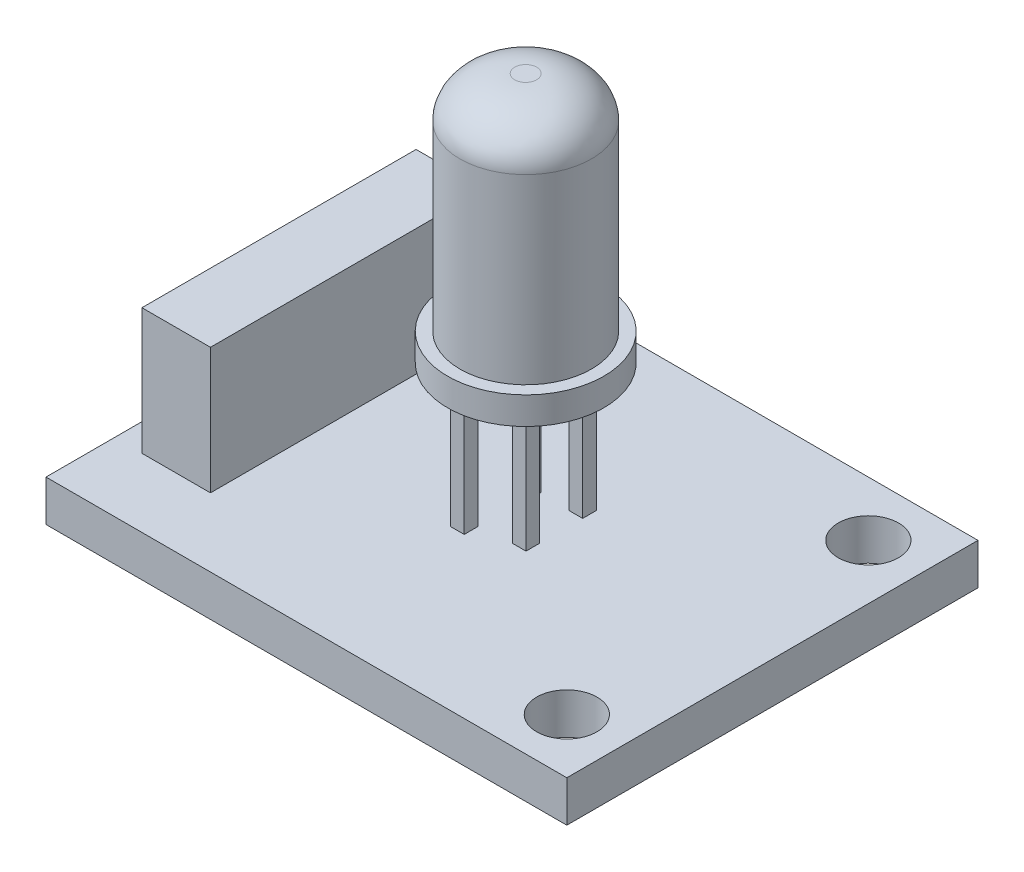
SolidWorks part; units mm, degrees
ref_plane "前视基准面" through (0, 0, 0) normal (0, 0, 1) x (1, 0, 0)
ref_plane "上视基准面" through (0, 0, 0) normal (0, 1, 0) x (1, 0, 0)
ref_plane "右视基准面" through (0, 0, 0) normal (1, 0, 0) x (0, 0, -1)
other "Configuration Table"
sketch "草图1" plane through (0, 0, 0) normal (0, 1, 0) x (1, 0, 0)
  line L1 (0, 0) -> (19, 0)
  line L2 (0, 0) -> (0, 15)
  line L3 (0, 15) -> (19, 15)
  line L4 (19, 0) -> (19, 15)
  line L5 (1, 12.5) -> (3.5, 12.5)
  line L6 (1, 12.5) -> (1, 2.5)
  line L7 (1, 2.5) -> (3.5, 2.5)
  line L8 (3.5, 12.5) -> (3.5, 2.5)
  line L9 (8.9417, 6.3147) -> (9.4417, 6.3147)
  line L10 (8.9417, 6.3147) -> (8.9417, 5.8147)
  line L11 (8.9417, 5.8147) -> (9.4417, 5.8147)
  line L12 (9.4417, 6.3147) -> (9.4417, 5.8147)
  line L13 (9.0122, 8.548) -> (9.5122, 8.548)
  line L14 (9.0122, 8.548) -> (9.0122, 8.048)
  line L15 (9.0122, 8.048) -> (9.5122, 8.048)
  line L16 (9.5122, 8.548) -> (9.5122, 8.048)
  line L17 (10.596, 6.9144) -> (11.096, 6.9144)
  line L18 (10.596, 6.9144) -> (10.596, 6.4144)
  line L19 (10.596, 6.4144) -> (11.096, 6.4144)
  line L20 (11.096, 6.9144) -> (11.096, 6.4144)
  line L21 (10.596, 8.9822) -> (11.096, 8.9822)
  line L22 (10.596, 8.9822) -> (10.596, 8.4822)
  line L23 (10.596, 8.4822) -> (11.096, 8.4822)
  line L24 (11.096, 8.9822) -> (11.096, 8.4822)
  circle A0 centre (10, 7.5) radius 2.85
  circle A1 centre (17, 13) radius 1.1
  circle A2 centre (17, 2) radius 1.1
  circle A3 centre (10, 7.5) radius 2.4
  point P15 (0, 7.5)
  point P16 (1, 7.5)
  dimension "D3" = 1
  dimension "D6" = 5.7
  dimension "D7" = 4.8
  dimension "D9" = 2.2
  dimension "D1" = 19
  dimension "D2" = 15
  dimension "D4" = 2.5
  dimension "D5" = 10
  dimension "D8" = 9
  dimension "D10" = 2
  dimension "D11" = 2
  dimension "D12" = 2
extrude "凸台-拉伸1" add sketch "草图1" against normal blind 1.5 contours L1 L4 L3 L2 A2 A1 A0 L5 L8 L7 L6 | L8 L5 L6 L7 | A0 region at (0.2421, 0, -7.5) region at (2.25, 0, -7.5)
extrude "凸台-拉伸2" add sketch "草图1<4>" along normal blind 14 contours A3
sketch "草图1<4>" plane through (0, 0, 0) normal (0, 1, 0) x (1, 0, 0) same geometry as "草图1"
extrude "凸台-拉伸3" add sketch "草图1<5>" along normal blind 5.86 contours A0
sketch "草图1<5>" plane through (0, 0, 0) normal (0, 1, 0) x (1, 0, 0) same geometry as "草图1"
extrude "切除-拉伸1" cut sketch "草图1<7>" along normal blind 4.86 contours A0
sketch "草图1<7>" plane through (0, 0, 0) normal (0, 1, 0) x (1, 0, 0) same geometry as "草图1"
extrude "凸台-拉伸4" add sketch "草图1<8>" along normal up to surface (4.86 mm away) contours L16 L13 L14 L15 | L12 L9 L10 L11 | L20 L17 L18 L19 | L24 L21 L22 L23 region at (9.1917, 0, -6.0647) region at (9.2622, 0, -8.298) region at (10.846, 0, -6.6644) region at (10.846, 0, -8.7322) up to face at (10, 4.86, -4.65)
sketch "草图1<8>" plane through (0, 0, 0) normal (0, 1, 0) x (1, 0, 0) same geometry as "草图1"
fillet "圆角3" radius 1.5 1 edges at (10, 14, -5.1) second distance 2 first distance on face at (10, 5.86, -5.1)
extrude "凸台-拉伸5" add sketch "草图1<9>" along normal blind 4.6 contours L8 L5 L6 L7 region at (2.25, 0, -7.5)
sketch "草图1<9>" plane through (0, 0, 0) normal (0, 1, 0) x (1, 0, 0) same geometry as "草图1"
